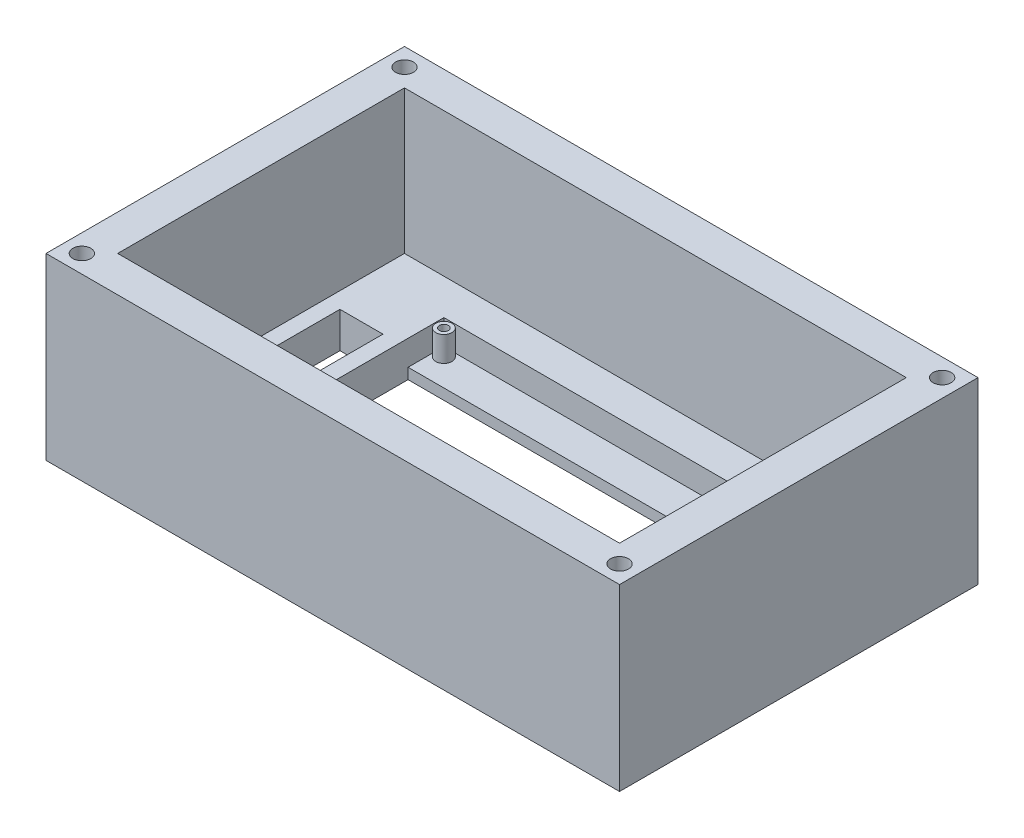
SolidWorks part; units mm, degrees
ref_plane "Plan de face" through (0, 0, 0) normal (0, 0, 1) x (1, 0, 0)
ref_plane "Plan de dessus" through (0, 0, 0) normal (0, 1, 0) x (1, 0, 0)
ref_plane "Plan de droite" through (0, 0, 0) normal (1, 0, 0) x (0, 0, -1)
sketch "Esquisse1" plane through (0, 0, 0) normal (0, 1, 0) x (1, 0, 0)
  line L1 (0, 0) -> (160, 0)
  line L2 (0, 0) -> (0, 100)
  line L3 (0, 100) -> (160, 100)
  line L4 (160, 0) -> (160, 100)
  dimension "D1" = 160
  dimension "D2" = 100
extrude "Boss.-Extru.1" add sketch "Esquisse1" along normal blind 50
shell "Coque1" thickness 10 removed face at (80, 50, -50)
sketch "Esquisse2" plane through (0, 50, 0) normal (0, 1, 0) x (1, 0, 0)
  line L0 (160, 0) -> (160, 100) construction
  line L1 (160, 100) -> (0, 100) construction
  line L2 (0, 0) -> (160, 0) construction
  line L3 (0, 100) -> (0, 0) construction
  circle A0 centre (155, 95) radius 2.5
  circle A1 centre (155, 5) radius 2.5
  circle A2 centre (5, 5) radius 2.5
  circle A3 centre (5, 95) radius 2.5
  dimension "D1" = 5
  dimension "D4" = 5
  dimension "D5" = 5
  dimension "D6" = 5
  dimension "D2" = 5
  dimension "D3" = 5
  dimension "D7" = 5
  dimension "D8" = 5
  dimension "D9" = 5
  dimension "D10" = 5
  dimension "D11" = 5
  dimension "D12" = 5
extrude "Enlèv. mat.-Extru.2" cut sketch "Esquisse2" against normal blind 15 contours A2 | A1 | A0 | A3
sketch "Esquisse3" plane through (0, 10, 0) normal (0, 1, 0) x (1, 0, 0)
  line L0 (150, 90) -> (10, 90) construction
  line L1 (31, 80) -> (129, 80)
  line L2 (31, 80) -> (31, 20)
  line L3 (31, 20) -> (129, 20)
  line L4 (129, 80) -> (129, 20)
  line L5 (31, 70) -> (129, 70)
  line L6 (31, 70) -> (31, 30)
  line L7 (31, 30) -> (129, 30)
  line L8 (129, 70) -> (129, 30)
  line L11 (10, 90) -> (10, 10) construction
  circle A0 centre (33.5, 77.5) radius 1.25
  circle A1 centre (33.5, 22.5) radius 1.25
  circle A2 centre (126.5, 77.5) radius 1.25
  circle A3 centre (126.5, 22.5) radius 1.25
  circle A4 centre (33.5, 77.5) radius 2.25
  circle A5 centre (126.5, 77.5) radius 2.25
  circle A6 centre (126.5, 22.5) radius 2.25
  circle A7 centre (33.5, 22.5) radius 2.25
  dimension "D3" = 2.5
  dimension "D4" = 2.5
  dimension "D5" = 2.5
  dimension "D6" = 2.5
  dimension "D10" = 2.5
  dimension "D21" = 4.5
  dimension "D22" = 4.5
  dimension "D23" = 4.5
  dimension "D24" = 4.5
  dimension "D1" = 98
  dimension "D2" = 60
  dimension "D7" = 2.5
  dimension "D8" = 2.5
  dimension "D9" = 2.5
  dimension "D11" = 2.5
  dimension "D12" = 2.5
  dimension "D13" = 2.5
  dimension "D14" = 2.5
  dimension "D15" = 40
  dimension "D16" = 10
  dimension "D17" = 10
  dimension "D18" = 21
extrude "Enlèv. mat.-Extru.3" cut sketch "Esquisse3" against normal blind 10 contours L5 L8 L7 L6
extrude "Enlèv. mat.-Extru.4" cut sketch "Esquisse3<3>" against normal blind 10 contours A1 | A3 | A2 | A0
sketch "Esquisse3<3>" plane through (0, 10, 0) normal (0, 1, 0) x (1, 0, 0) same geometry as "Esquisse3"
extrude "Enlèv. mat.-Extru.5" cut sketch "Esquisse3<5>" against normal blind 7 contours L1 L4 L3 L2
sketch "Esquisse3<5>" plane through (0, 10, 0) normal (0, 1, 0) x (1, 0, 0) same geometry as "Esquisse3"
extrude "Boss.-Extru.2" add sketch "Esquisse3<6>" against normal blind 7 separate body contours A7 | A4 | A5 | A6 | A1 | A0 | A2 | A3
sketch "Esquisse3<6>" plane through (0, 10, 0) normal (0, 1, 0) x (1, 0, 0) same geometry as "Esquisse3"
sketch "Esquisse4" plane through (0, 10, 0) normal (0, 1, 0) x (1, 0, 0)
  line L0 (150, 90) -> (10, 90) construction
  line L1 (14.5, 67.5) -> (26.5, 67.5)
  line L2 (14.5, 67.5) -> (14.5, 32.5)
  line L3 (14.5, 32.5) -> (26.5, 32.5)
  line L4 (26.5, 67.5) -> (26.5, 32.5)
  line L8 (10, 90) -> (10, 10) construction
  line L9 (150, 90) -> (10, 90) construction
  line L10 (133.5, 67.5) -> (145.5, 67.5)
  line L11 (133.5, 67.5) -> (133.5, 32.5)
  line L12 (133.5, 32.5) -> (145.5, 32.5)
  line L13 (145.5, 67.5) -> (145.5, 32.5)
  line L14 (150, 10) -> (150, 90) construction
  dimension "D1" = 12
  dimension "D2" = 35
  dimension "D3" = 22.5
  dimension "D4" = 4.5
  dimension "D5" = 12
  dimension "D6" = 35
  dimension "D7" = 22.5
  dimension "D8" = 4.5
extrude "Enlèv. mat.-Extru.6" cut sketch "Esquisse4" against normal blind 10
